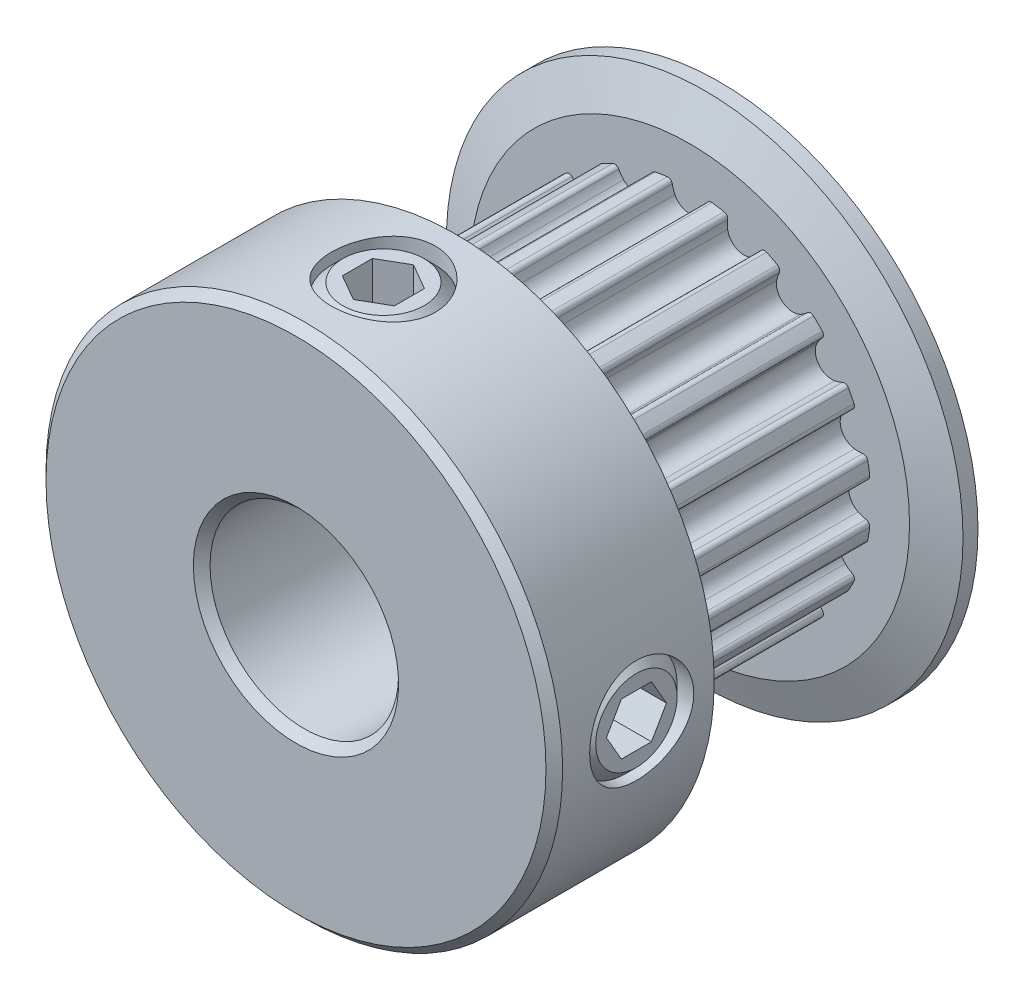
SolidWorks part; units mm, degrees
ref_plane "Front Plane" through (0, 0, 0) normal (0, 0, 1) x (1, 0, 0)
ref_plane "Top Plane" through (0, 0, 0) normal (0, 1, 0) x (1, 0, 0)
ref_plane "Right Plane" through (0, 0, 0) normal (1, 0, 0) x (0, 0, -1)
sketch "Sketch1" plane through (0, 0, 0) normal (0, 0, 1) x (1, 0, 0)
  line L1 (-1.7499, 5.3585) -> (1.7499, 5.3585) construction
  line L4 (0, 0) -> (0, 5.3585) construction
  line L5 (0, 5.3585) -> (0, 11.2243) construction
  line L6 (0, 6.3625) -> (1.9751, 6.0482) construction
  line L7 (1.9751, 6.0482) -> (2.6648, 5.8229) construction
  line L8 (1.9751, 6.0482) -> (1.7499, 5.3585) construction
  line L9 (-1.9751, 6.0482) -> (-1.7499, 5.3585) construction
  line L10 (-1.8963, 5.8067) -> (-2.841, 8.6995)
  line L11 (-2.841, 8.6995) -> (2.841, 8.6995)
  line L12 (2.841, 8.6995) -> (1.8963, 5.8067)
  circle A0 centre (0, 0) radius 6.3625 construction
  circle A1 centre (0, 0) radius 8.6995 construction
  circle A2 centre (0, 0) radius 6.1085 construction
  arc A3 (-0.4989, 5.6703) -> (0.4989, 5.6703) centre (0, 5.9135) ccw
  arc A4 (-0.4989, 5.6703) -> (-0.5855, 5.9387) centre (0.4, 6.1085) cw
  arc A5 (-1.8963, 5.8067) -> (-0.7518, 6.0621) centre (0, 0) cw
  arc A6 (-0.5855, 5.9387) -> (-0.7518, 6.0621) centre (-0.7333, 5.9132) ccw
  arc A7 (1.8963, 5.8067) -> (0.7518, 6.0621) centre (0, 0) ccw
  arc A8 (0.5855, 5.9387) -> (0.7518, 6.0621) centre (0.7333, 5.9132) cw
  arc A9 (0.4989, 5.6703) -> (0.5855, 5.9387) centre (-0.4, 6.1085) ccw
  point P6 (0, 20.9083)
  point P11 (0, 6.3625)
  point P13 (0, 8.6995)
  point P14 (0, 6.1085)
  dimension "D1" = 9.684
  dimension "D2" = 4.8618
sketch "Sketch2" plane through (0, 0, 0) normal (1, 0, 0) x (0, 0, -1)
  line L0 (-7.135, 3.175) -> (7.135, 3.175)
  line L1 (-7.135, 3.175) -> (-7.135, 8.6995)
  line L2 (-1.75, 8.6995) -> (-7.135, 8.6995)
  line L3 (-2.255, 3.175) -> (-2.255, 8.6995) construction
  line L4 (-2.255, 8.6995) -> (-1.245, 8.6995) construction
  line L5 (-1.245, 8.6995) -> (-1.245, 6.1085) construction
  line L6 (-1.245, 6.1085) -> (6.125, 6.1085)
  line L7 (6.125, 6.1085) -> (6.125, 8.6995) construction
  line L8 (6.125, 8.6995) -> (7.135, 8.6995) construction
  line L9 (7.135, 8.6995) -> (7.135, 3.175)
  line L10 (-7.135, 0) -> (7.135, 0) construction
  line L11 (6.63, 8.6995) -> (6.125, 7.404)
  line L12 (-1.245, 7.404) -> (-1.75, 8.6995)
  line L14 (-1.245, 7.404) -> (-1.245, 6.1085)
  line L15 (6.125, 6.1085) -> (6.125, 7.404)
  line L16 (6.63, 8.6995) -> (7.135, 8.6995)
  arc A0 (-1.245, 7.404) -> (-1.75, 8.6995) centre (-3.1592, 7.404) ccw construction
  arc A1 (6.125, 7.404) -> (6.63, 8.6995) centre (8.0392, 7.404) cw construction
  point P12 (-1.245, 7.404)
  point P14 (-1.75, 8.6995)
  point P20 (6.125, 7.404)
  point P21 (6.63, 8.6995)
  point P25 (6.125, 0)
  point P26 (-1.245, 0)
  dimension "OA" = 14.27
  dimension "Bore" = 6.35
  dimension "Outside Width" = 8.38
  dimension "Inside Width" = 7.37
revolve "Revolve1" add sketch "Sketch2" angle 360 mid plane about L10
sketch "Sketch3" plane through (0, 0, 0) normal (0, 0, 1) x (1, 0, 0)
  line L6 (2.841, 8.6995) -> (-2.841, 8.6995)
  line L7 (1.8963, 5.8067) -> (2.841, 8.6995)
  line L8 (-2.841, 8.6995) -> (-1.8963, 5.8067)
  line L9 (2.841, 8.6995) -> (-2.841, 8.6995)
  line L10 (1.8963, 5.8067) -> (2.841, 8.6995)
  line L11 (-2.841, 8.6995) -> (-1.8963, 5.8067)
  arc A8 (1.8963, 5.8067) -> (0.7518, 6.0621) centre (0, 0) ccw
  arc A9 (0.7518, 6.0621) -> (0.5855, 5.9387) centre (0.7333, 5.9132) ccw
  arc A10 (0.4989, 5.6703) -> (0.5855, 5.9387) centre (-0.4, 6.1085) ccw
  arc A11 (-0.4989, 5.6703) -> (0.4989, 5.6703) centre (0, 5.9135) ccw
  arc A12 (-0.5855, 5.9387) -> (-0.4989, 5.6703) centre (0.4, 6.1085) ccw
  arc A13 (-0.5855, 5.9387) -> (-0.7518, 6.0621) centre (-0.7333, 5.9132) ccw
  arc A14 (-0.7518, 6.0621) -> (-1.8963, 5.8067) centre (0, 0) ccw
  arc A15 (1.8963, 5.8067) -> (0.7518, 6.0621) centre (0, 0) ccw
  arc A16 (0.7518, 6.0621) -> (0.5855, 5.9387) centre (0.7333, 5.9132) ccw
  arc A17 (0.4989, 5.6703) -> (0.5855, 5.9387) centre (-0.4, 6.1085) ccw
  arc A18 (-0.4989, 5.6703) -> (0.4989, 5.6703) centre (0, 5.9135) ccw
  arc A19 (-0.5855, 5.9387) -> (-0.4989, 5.6703) centre (0.4, 6.1085) ccw
  arc A20 (-0.5855, 5.9387) -> (-0.7518, 6.0621) centre (-0.7333, 5.9132) ccw
  arc A21 (-0.7518, 6.0621) -> (-1.8963, 5.8067) centre (0, 0) ccw
  dimension "D1" = 0
extrude "Cut-Extrude1" cut sketch "Sketch3" against normal up to vertex (6.125 mm away) from vertex up to point (0, 6.1085, -6.125) starting at point (0, 6.1085, 1.245)
pattern_circular "CirPattern1" count 20 over 360 about axis through (0, 0, 7.135) along (0, 0, 1) of "Cut-Extrude1"
sketch "Sketch4" plane through (0, 0, 0) normal (1, 0, 0) x (0, -1, 0)
  line L0 (0, -1.245) -> (0, -7.135) construction
  line L1 (-3.175, -7.135) -> (3.175, -7.135) construction
  line L2 (7.404, -1.245) -> (-7.404, -1.245) construction
  circle A0 centre (0, -4.19) radius 1.7526
extrude "Cut-Extrude2" cut sketch "Sketch4" along normal through all
ref_plane "Plane1" through (0, 0, 4.19) normal (0, 0, 1) x (1, 0, 0)
sketch "Sketch5" plane through (0, 0, 4.19) normal (0, 0, 1) x (1, 0, 0)
  line L0 (0, 0) -> (0, 8.6995) construction
  line L1 (3.175, -1.3716) -> (3.175, 0)
  line L2 (3.556, -1.7526) -> (8.1401, -1.7526)
  line L3 (3.175, 0) -> (8.6995, 0) construction
  line L4 (3.175, 0) -> (8.5211, 0)
  line L5 (8.5211, 0) -> (8.5211, -1.3716)
  line L6 (3.556, -1.7526) -> (3.175, -1.3716)
  line L7 (8.5211, -1.3716) -> (8.1401, -1.7526)
  circle A0 centre (0, 0) radius 8.6995 construction
  circle A1 centre (0, 0) radius 3.175 construction
  point P2 (3.175, -1.7526)
  point P11 (8.5211, -1.7526)
revolve "Revolve2" add sketch "Sketch5" angle 360 mid plane about L4
sketch "Sketch6" plane through (8.5211, 5.3841, 0) normal (-1, 0, 0) x (0, -1, 0)
  line L1 (5.3841, 5.2019) -> (4.5078, 4.6959)
  line L2 (4.5078, 4.6959) -> (4.5078, 3.6841)
  line L3 (4.5078, 3.6841) -> (5.3841, 3.1781)
  line L4 (5.3841, 3.1781) -> (6.2604, 3.6841)
  line L5 (6.2604, 3.6841) -> (6.2604, 4.6959)
  line L6 (6.2604, 4.6959) -> (5.3841, 5.2019)
  circle A0 centre (5.3841, 4.19) radius 0.8763 construction
  dimension "D1" = 1.7526
extrude "Cut-Extrude3" cut sketch "Sketch6" along normal blind 1.3144
pattern_circular "CirPattern3" count 2 over 90 about axis through (0, 0, 7.135) along (0, 0, 1) of "Cut-Extrude2", "Revolve2", "Cut-Extrude3"
chamfer "Chamfer1" distance 0.2807 angle 45 2 edges at (3.175, 0, 7.135) (8.6995, 0, 7.135)
ref_axis "Center Axis 1" through (0, 0, -7.135) along (0, 0, 1)
ref_plane "Contact Plane 1" through (0, 0, 7.135) normal (0, 0, 1) x (1, 0, 0)
ref_plane "Contact Plane 2" through (0, 0, -7.135) normal (0, 0, -1) x (-1, 0, 0)
equation "\"D2@Sketch1\"= \"D1@Sketch1\" / 2"
equation "\"D1@Sketch6\" = \"Set Screw@Sketch4\" / 2"
equation "\"D1@Cut-Extrude3\" = \"D1@Sketch6\"*.75"
